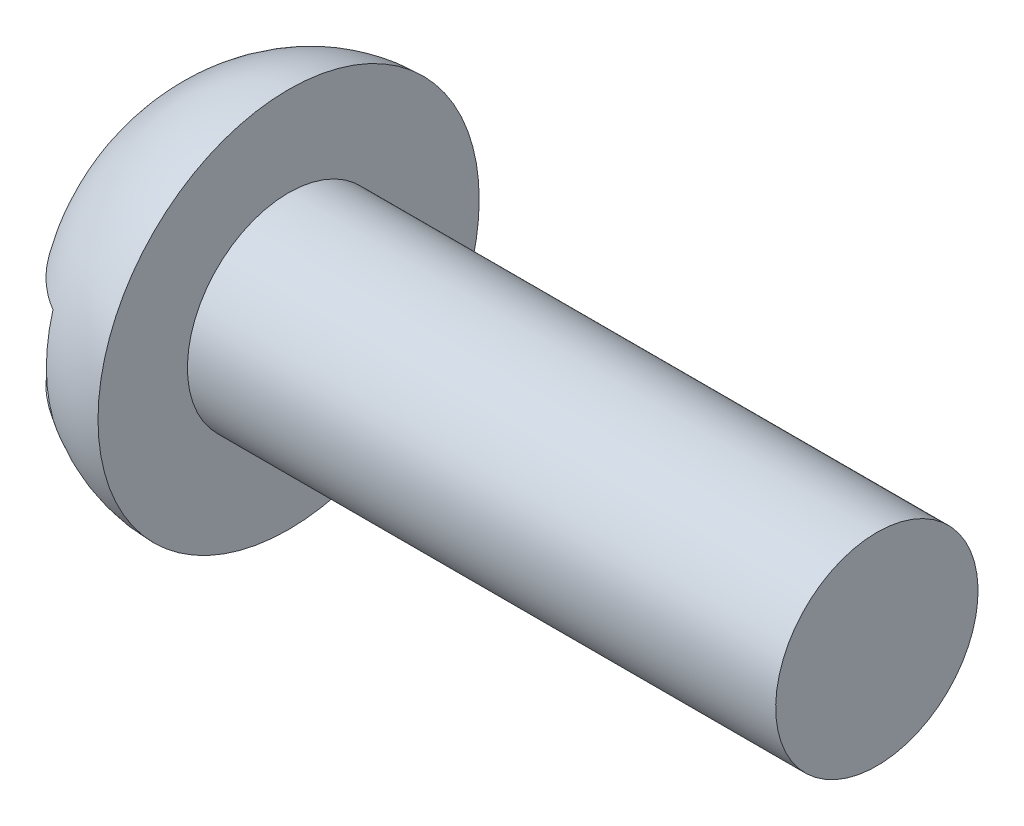
SolidWorks part; units mm, degrees
ref_plane "Front Plane" through (0, 0, 0) normal (0, 0, 1) x (1, 0, 0)
ref_plane "Top Plane" through (0, 0, 0) normal (0, 1, 0) x (1, 0, 0)
ref_plane "Right Plane" through (0, 0, 0) normal (1, 0, 0) x (0, 0, -1)
sketch "Sketch2" plane through (0, 0, 0) normal (0, 0, 1) x (1, 0, 0)
  line L0 (0, 2.0574) -> (0, 1.0922)
  line L1 (0, 1.0922) -> (6.35, 1.0922)
  line L2 (6.35, 1.0922) -> (6.35, 0)
  line L3 (6.35, 0) -> (0, 0)
  line L4 (0, 0) -> (-1.7526, 0)
  ellipse E0 centre (0, 0) end of major axis (0, -2.0574) minor radius 1.7526 (0, 2.0574) -> (-1.7526, 0) ccw
  dimension "D1" = 2.0574
  dimension "D2" = 1.7526
  dimension "D3" = 6.35
  dimension "D4" = 1.0922
revolve "Revolve1" add sketch "Sketch2" angle 360 about L3
sketch3d "3DSketch1"
  line L0 (0, 0, 0) -> (0, 0.508, 0) construction
  line L1 (0, 0.508, 0) -> (-0.762, 0.508, 0) construction
  line L2 (-0.762, 0.508, 0) -> (-0.762, -0.508, 0)
  line L3 (-0.762, -0.508, 0) -> (0, -0.508, 0) construction
  line L4 (0, -0.508, 0) -> (0, 0, 0) construction
  line L5 (-0.762, 0.508, 0) -> (-3.302, 0.508, 0)
  line L6 (-3.302, 0.508, 0) -> (-3.302, -0.508, 0)
  line L7 (-3.302, -0.508, 0) -> (-0.762, -0.508, 0)
  line L8 (-0.762, 0.508, 0) -> (-0.762, 0.508, 0.1843) construction
  point P8 (0, 0, 0)
  dimension "D1" = 0.508
  dimension "D2" = 1.016
  dimension "D3" = 0.762
  dimension "D4" = 0.762
  dimension "D5" = 1.016
  dimension "D6" = 2.54
extrude "Cut-Extrude1" cut sketch "3DSketch1" along direction (0, 0, 1) on the side against the normal blind 2.54 and the other way blind 2.54 contours L6 L7 L2 L5
